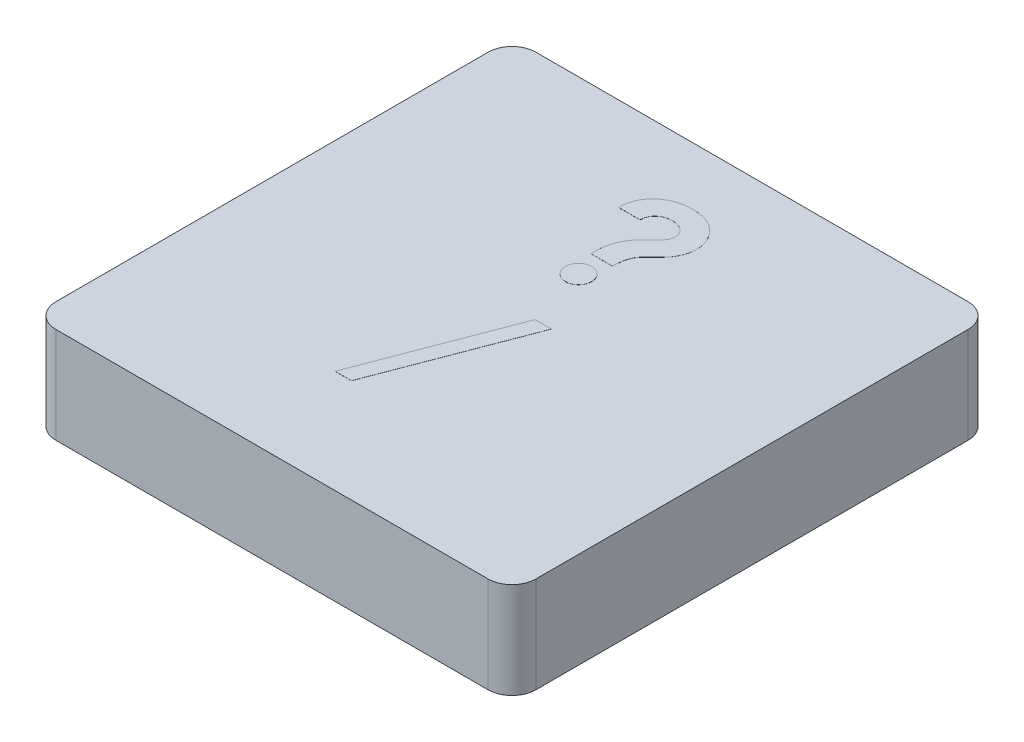
SolidWorks part; units mm, degrees
ref_plane "Front Plane" through (0, 0, 0) normal (0, 0, 1) x (1, 0, 0)
ref_plane "Top Plane" through (0, 0, 0) normal (0, 1, 0) x (1, 0, 0)
ref_plane "Right Plane" through (0, 0, 0) normal (1, 0, 0) x (0, 0, -1)
sketch "Sketch1" plane through (0, 0, 0) normal (0, 1, 0) x (1, 0, 0)
  line L0 (0, 0) -> (12.7, 0)
  line L1 (12.7, 0) -> (12.7, 12.7)
  line L2 (12.7, 12.7) -> (0, 12.7)
  line L3 (0, 12.7) -> (0, 0)
  dimension "D1" = 12.7
  dimension "D2" = 12.7
extrude "Boss-Extrude1" add sketch "Sketch1" along normal blind 2.54
fillet "Fillet1" radius 0.635 4 edges at (0, 1.27, -12.7) (12.7, 1.27, -12.7) (12.7, 1.27, 0) (0, 1.27, 0)
shell "Shell1" thickness 0.635 removed face at (6.35, 0, -6.35)
sketch "Sketch2" plane through (0, 1.905, 0) normal (0, -1, 0) x (-1, 0, 0)
  line L0 (-0.635, 6.35) -> (-12.065, 6.35) construction
  line L1 (-0.635, 12.065) -> (-0.635, 0.635) construction
  line L2 (-12.065, 0.635) -> (-12.065, 12.065) construction
  line L3 (-6.35, 0.635) -> (-6.35, 12.065) construction
  line L4 (-0.635, 0.635) -> (-12.065, 0.635) construction
  line L5 (-12.065, 12.065) -> (-0.635, 12.065) construction
  circle A0 centre (-6.35, 6.35) radius 2.54
  dimension "D1" = 5.08
extrude "Boss-Extrude2" add sketch "Sketch2" along normal up to surface (1.905 mm away) up to face at (6.35, 0, -6.35)
sketch "Sketch3" plane through (0, 2.54, 0) normal (0, 1, 0) x (1, 0, 0)
  line L0 (0.635, 0) -> (12.065, 0) construction
  line L1 (0, 12.065) -> (0, 0.635) construction
  line L2 (12.065, 12.7) -> (0.635, 12.7) construction
  text T0 "<b>?</b>"
  text T1 "<b>/</b>"
  dimension "D1" = 3.302
  dimension "D2" = 5.207
  dimension "D3" = 4.826
  dimension "D4" = 5.08
extrude "Boss-Extrude3" add sketch "Sketch3" along normal blind 0.0025
